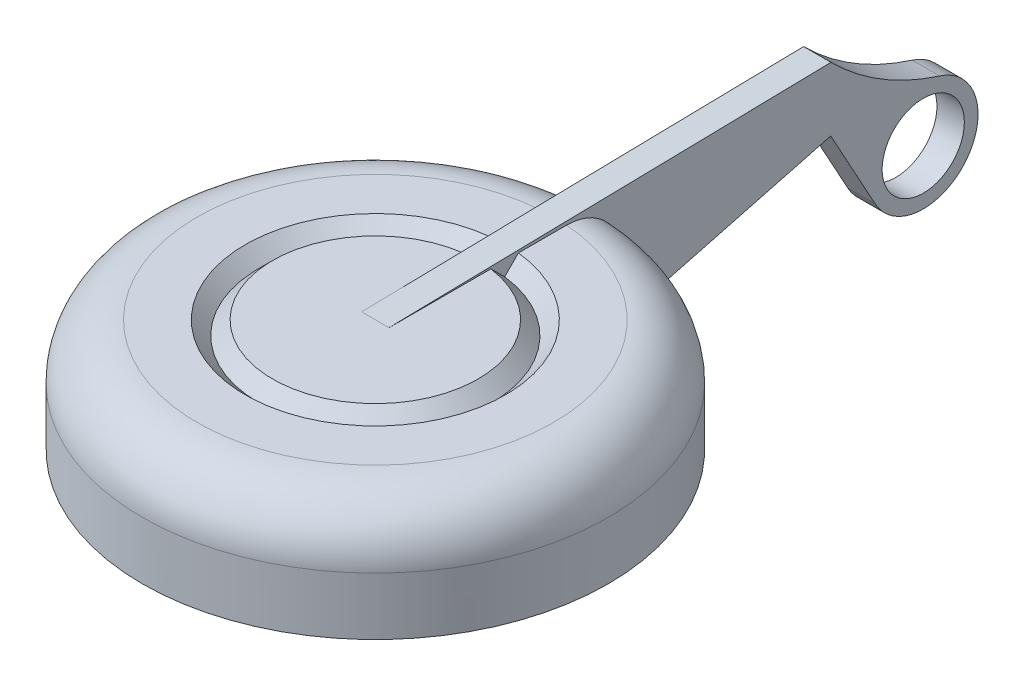
SolidWorks part; units mm, degrees
ref_plane "Front Plane" through (0, 0, 0) normal (0, 0, 1) x (1, 0, 0)
ref_plane "Top Plane" through (0, 0, 0) normal (0, 1, 0) x (1, 0, 0)
ref_plane "Right Plane" through (0, 0, 0) normal (1, 0, 0) x (0, 0, -1)
sketch "Sketch4" plane through (0, 0, 0) normal (1, 0, 0) x (0, 0, -1)
  line L0 (0, 0) -> (-3.75, 0)
  line L1 (-3.75, 0) -> (-4.25, -0.5)
  line L2 (-4.25, -0.5) -> (-4.75, 0)
  line L3 (-4.75, 0) -> (-8.5, 0)
  line L4 (-8.5, 0) -> (-8.5, -4)
  line L5 (-8.5, -4) -> (0, -4)
  line L6 (0, 0) -> (0, -4)
  line L7 (-8.5, -0.5) -> (0, -0.5) construction
  line L8 (0, 1.8905) -> (0, -6.6755) construction
  point P3 (-4.25, -0.5)
  dimension "D1" = 8.5
  dimension "D2" = 0.5
  dimension "D3" = 4
revolve "Revolve1" add sketch "Sketch4" angle 360 about L8
fillet "Fillet1" radius 2 1 edges at (0, 0, 8.5)
sketch "Sketch5" plane through (0, -4, 0) normal (0, -1, 0) x (1, 0, 0)
  circle A0 centre (0, 0) radius 8.5
  circle A1 centre (0, 0) radius 7
  dimension "D1" = 14
extrude "Boss-Extrude1" add sketch "Sketch5" along normal blind 0.1 separate body
sketch "Sketch6" plane through (0, 0, 0) normal (1, 0, 0) x (0, 0, -1)
  line L0 (0, 0) -> (16.1329, 0.32)
  line L1 (8.5, -4) -> (16.1218, -1.9998)
  line L2 (8.5, -4) -> (8.5, -2) construction
  line L3 (8.5, -4) -> (-8.5, -4) construction
  line L4 (16.1218, -1.9998) -> (17.7464, -4.9618)
  line L5 (0, 0) -> (0, -0.9077)
  line L6 (0, -0.9077) -> (7.1744, -0.9077)
  line L7 (7.1744, -0.9077) -> (8.5, -4)
  circle A0 centre (19.5, -4) radius 1.5
  circle A1 centre (19.5, -4) radius 2
  arc A2 (16.1329, 0.32) -> (20.0986, -2.0917) centre (22.992, 7.1325) ccw
  dimension "D1" = 3
  dimension "D2" = 4
  dimension "D3" = 19.5
extrude "Boss-Extrude2" add sketch "Sketch6" along normal blind 0.5 and the other way blind 0.5 contours A2 L0 L5 L6 L7 L1 L4 A1 | A1 A0 region at (0, -1.316, -11.0115) region at (0, -2.8497, -21.0664)
